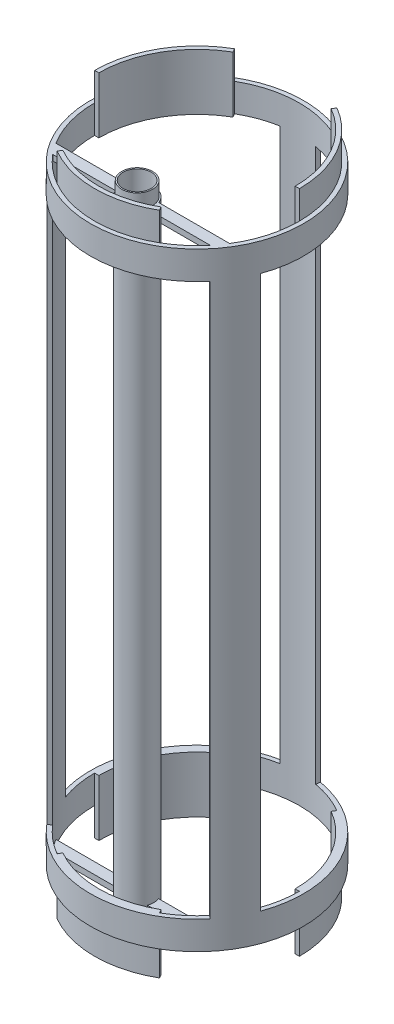
SolidWorks part; units mm, degrees
ref_plane "Спереди" through (0, 0, 0) normal (0, 0, 1) x (1, 0, 0)
ref_plane "Сверху" through (0, 0, 0) normal (0, 1, 0) x (1, 0, 0)
ref_plane "Справа" through (0, 0, 0) normal (1, 0, 0) x (0, 0, -1)
other "Configuration Table"
sketch "Эскиз1" plane through (0, 0, 0) normal (0, 1, 0) x (1, 0, 0)
  line L0 (0, 0) -> (0, 37.85)
  line L1 (0, 0) -> (6.5726, 37.275)
  line L2 (0, 0) -> (-6.5726, 37.275)
  line L3 (0, 0) -> (35.5674, -12.9455)
  line L4 (0, 0) -> (32.7791, -18.925)
  line L5 (0, 0) -> (28.9948, -24.3295)
  line L6 (0, 0) -> (-28.9948, -24.3295)
  line L7 (0, 0) -> (-32.7791, -18.925)
  line L8 (0, 0) -> (-35.5674, -12.9455)
  line L9 (0, 0) -> (0, -37.85)
  line L10 (0, 0) -> (18.925, -32.7791)
  line L11 (0, 0) -> (-18.925, -32.7791)
  line L12 (0, 0) -> (-37.85, 0)
  line L13 (0, 0) -> (-32.7791, 18.925)
  line L14 (0, 0) -> (-18.925, 32.7791)
  line L15 (0, 0) -> (18.925, 32.7791)
  line L16 (0, 0) -> (32.7791, 18.925)
  line L17 (0, 0) -> (37.85, 0)
  line L18 (0, 0) -> (0, -21.25)
  line L19 (-6, -21.25) -> (-27.6217, -21.25) construction
  line L20 (6, -21.25) -> (27.6217, -21.25) construction
  line L21 (-30.8344, -19.25) -> (-5.6569, -19.25)
  line L22 (-5.6569, -23.25) -> (-27.9421, -23.25)
  line L23 (30.8344, -19.25) -> (5.6569, -19.25)
  line L24 (27.9421, -23.25) -> (5.6569, -23.25)
  circle A0 centre (0, 0) radius 37.85
  circle A1 centre (0, 0) radius 36.35
  circle A2 centre (0, 0) radius 34.85
  circle A3 centre (0, -21.25) radius 6
  circle A4 centre (0, -21.25) radius 5.5
  circle A5 centre (0, -21.25) radius 5
  point P16 (0, 0)
  point P27 (0, 0)
  dimension "D1" = 75.7
  dimension "D2" = 1.5
  dimension "D6" = 1.5
  dimension "D11" = 10
  dimension "D12" = 11
  dimension "D13" = 12
  dimension "D14" = 2
  dimension "D3" = 10
  dimension "D4" = 10
  dimension "D5" = 3
  dimension "D7" = 30
  dimension "D8" = 30
  dimension "D10" = 21.25
  dimension "D15" = 2
  dimension "D16" = 2
  dimension "D17" = 2
  dimension "D9" = 3
extrude "Бобышка-Вытянуть1" add sketch "Эскиз1" along normal blind 10 contours A0 | A1
extrude "Бобышка-Вытянуть6" add sketch "Эскиз1<7>" along normal blind 2 contours A2 L21 A1 L22 L6 | L6 A2 L22 L11 L21 | L21 A2 L6 | A2 L6 L22 | A3 L21 L11 L22 | A2 L24 L5 | A2 L5 L24 A1 L23 | L5 A2 L23 | L24 A2 L5 L23 L10 | A3 L24 L10 L23 region at (26.2544, 0, 20.3084) region at (18.7384, 0, 21.289) region at (-18.7384, 0, 21.289) region at (-26.2544, 0, 20.3084) region at (9.1118, 0, 21.3706) region at (-9.1118, 0, 21.3706) region at (28.6801, 0, 21.1012) region at (26.7907, 0, 22.9677) region at (-26.7907, 0, 22.9677) region at (-28.6801, 0, 21.1012)
sketch "Эскиз1<7>" plane through (0, 0, 0) normal (0, 1, 0) x (1, 0, 0) same geometry as "Эскиз1"
extrude "Бобышка-Вытянуть7" add sketch "Эскиз1<8>" against normal blind 5 separate body contours A5 L9 A4 | A5 L9 A4 region at (3.8021, 0, 17.4479) region at (-0.123, 0, 16)
sketch "Эскиз1<8>" plane through (0, 0, 0) normal (0, 1, 0) x (1, 0, 0) same geometry as "Эскиз1"
extrude "Бобышка-Вытянуть8" add sketch "Эскиз1<9>" along normal blind 10 and the other way blind 10 contours A2 L9 A1 L10 | A2 L11 A1 L9 | A2 L13 A1 L12 | A2 L14 A1 L13 | A2 L17 A1 L16 | A2 L16 A1 L15 region at (-34.0005, 0, -9.1104) region at (-24.8901, 0, -24.8901) region at (24.8901, 0, -24.8901) region at (34.0005, 0, -9.1104) region at (9.1104, 0, 34.0005) region at (-9.1104, 0, 34.0005)
sketch "Эскиз1<9>" plane through (0, 0, 0) normal (0, 1, 0) x (1, 0, 0) same geometry as "Эскиз1"
extrude "Бобышка-Вытянуть9" add sketch "Эскиз1<11>" along normal blind 215 contours A1 L1 A0 L0 | A1 L0 A0 L2 | A1 L5 A0 L4 | A1 L4 A0 L3 | A1 L7 A0 L6 | A1 L8 A0 L7 | A5 L9 A4 | A4 L9 A3 L18 | A5 L9 A4 | A4 L18 A3 L9 region at (3.3866, 0, 16.4606) region at (-0.1342, 0, 15.5) region at (-3.2298, 0, -36.917) region at (3.2298, 0, -36.917) region at (33.5859, 0, 15.6614) region at (30.3561, 0, 21.2556) region at (-30.3561, 0, 21.2556) region at (-33.5859, 0, 15.6614) region at (3.8021, 0, 17.4479) region at (-0.123, 0, 16)
sketch "Эскиз1<11>" plane through (0, 0, 0) normal (0, 1, 0) x (1, 0, 0) same geometry as "Эскиз1"
ref_plane "Плоскость1" through (0, 108, 0) normal (0, 1, 0) x (1, 0, 0)
mirror "Зеркальное отражение1" about plane through (0, 108, 0) normal (0, 1, 0) of bodies 113
